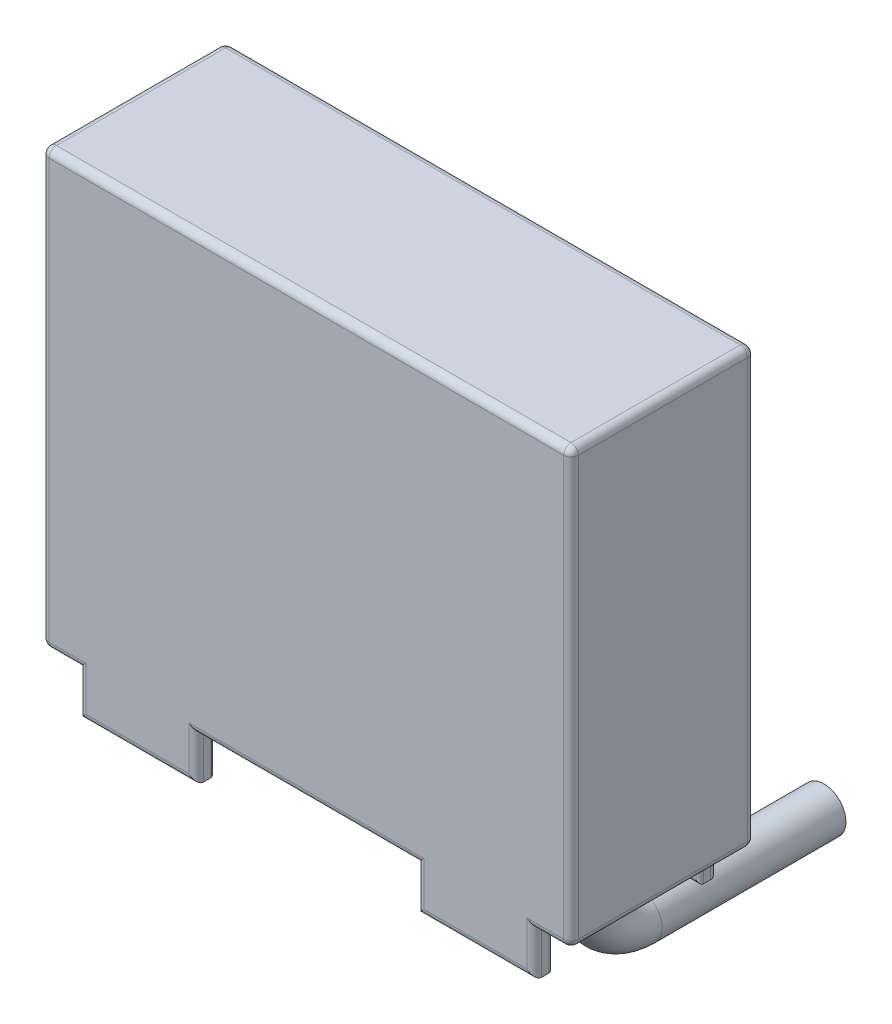
SolidWorks part; units mm, degrees
ref_plane "Front Plane" through (0, 0, 0) normal (0, 0, 1) x (1, 0, 0)
ref_plane "Top Plane" through (0, 0, 0) normal (0, 1, 0) x (1, 0, 0)
ref_plane "Right Plane" through (0, 0, 0) normal (1, 0, 0) x (0, 0, -1)
sketch "Sketch1" plane through (0, 0, 0) normal (0, 0, 1) x (1, 0, 0)
  line L1 (-3.6, 7) -> (3.6, 7)
  line L2 (-3.6, 7) -> (-3.6, 0.5)
  line L3 (-3.6, 0.5) -> (3.6, 0.5)
  line L4 (3.6, 7) -> (3.6, 0.5)
  line L5 (-3.6, 7) -> (3.6, 0.5) construction
  line L6 (-3.6, 0.5) -> (3.6, 7) construction
  point P0 (0, 3.75)
  dimension "D1" = 0.5
  dimension "D2" = 7.2
  dimension "D3" = 6.5
extrude "Boss-Extrude1" add sketch "Sketch1" along normal blind 2.5
sketch "Sketch5" plane through (0, 0.5, 0) normal (0, -1, 0) x (-1, 0, 0)
  line L0 (3.6, -2.5) -> (3.6, 0) construction
  line L1 (3.35, -2.25) -> (-3.35, -2.25)
  line L2 (3.35, -2.25) -> (3.35, -0.25)
  line L3 (3.35, -0.25) -> (-3.35, -0.25)
  line L4 (-3.35, -2.25) -> (-3.35, -0.25)
  line L5 (3.35, -2.25) -> (-3.35, -0.25) construction
  line L6 (3.35, -0.25) -> (-3.35, -2.25) construction
  line L7 (3.6, -2.5) -> (-3.6, -2.5) construction
  point P0 (0, -1.25)
  point P5 (3.35, -1.25)
  point P8 (3.6, -1.25)
  point P9 (0, -0.25)
  dimension "D1" = 0.25
  dimension "D2" = 0.25
extrude "Cut-Extrude1" cut sketch "Sketch5" against normal blind 0.7
sketch "Sketch6" plane through (0, 0, 2.5) normal (0, 0, 1) x (1, 0, 0)
  line L0 (-3.6, 0.5) -> (3.6, 0.5) construction
  line L1 (-1.5, 0.5) -> (1.5, 0.5)
  line L2 (-1.5, 0.5) -> (-1.5, 1.1)
  line L3 (-1.5, 1.1) -> (1.5, 1.1)
  line L4 (1.5, 0.5) -> (1.5, 1.1)
  line L6 (-3.6, 0.5) -> (-3.1, 0.5)
  line L7 (-3.6, 0.5) -> (-3.6, 1.1)
  line L8 (-3.6, 1.1) -> (-3.1, 1.1)
  line L9 (-3.1, 0.5) -> (-3.1, 1.1)
  line L10 (3.6, 0.5) -> (3.1, 0.5)
  line L11 (3.6, 0.5) -> (3.6, 1.1)
  line L12 (3.6, 1.1) -> (3.1, 1.1)
  line L13 (3.1, 0.5) -> (3.1, 1.1)
  point P16 (0, 0.5)
  dimension "D1" = 0.5
  dimension "D2" = 3
  dimension "D3" = 0.6
extrude "Cut-Extrude2" cut sketch "Sketch6" against normal blind 3
sketch "Sketch4" plane through (0, 1.2, 0) normal (0, -1, 0) x (1, 0, 0)
  line L0 (-2.54, 1.25) -> (2.54, 1.25) construction
  circle A0 centre (-2.54, 1.25) radius 0.3
  circle A1 centre (2.54, 1.25) radius 0.3
  point P2 (0, 1.25)
  dimension "D1" = 0.6
ref_plane "Plane1" through (-2.54, 0, 0) normal (1, 0, 0) x (0, 0, -1)
sketch "Sketch7" plane through (-2.54, 0, 0) normal (1, 0, 0) x (0, 0, -1)
  line L0 (-1.25, 1.2) -> (-1.25, 0.75)
  line L1 (-1.55, 1.2) -> (-0.95, 1.2) construction
  line L2 (-0.5, 0) -> (2, 0)
  arc A0 (-1.25, 0.75) -> (-0.5, 0) centre (-0.5, 0.75) ccw
  dimension "D2" = 0.75
  dimension "D1" = 2
sweep "Pin" add profiles "Sketch4" path "Sketch7"
fillet "Fillet1" radius 0.1 28 edges at (3.6, 7, 1.25) (3.6, 1.1, 1.25) (-3.6, 7, 1.25) (-3.6, 1.1, 1.25) (3.6, 4.05, 0) (0, 7, 0) (-3.6, 4.05, 0) (-3.35, 1.1, 0) (-3.1, 0.8, 0) (-2.3, 0.5, 0) (-1.5, 0.8, 0) (0, 1.1, 0) (1.5, 0.8, 0) (2.3, 0.5, 0) (3.1, 0.8, 0) (3.35, 1.1, 0) (2.3, 0.5, 2.5) (1.5, 0.8, 2.5) (0, 1.1, 2.5) (-1.5, 0.8, 2.5) (-2.3, 0.5, 2.5) (-3.1, 0.8, 2.5) (-3.35, 1.1, 2.5) (-3.6, 4.05, 2.5) (0, 7, 2.5) (3.6, 4.05, 2.5) (3.35, 1.1, 2.5) (3.1, 0.8, 2.5)
fillet "Fillet2" radius 0.05 30 edges at (-3.35, 1.1, 1.25) (3.35, 1.1, 1.25) (3.35, 1.15, 2.25) (0, 1.2, 2.25) (-3.35, 1.15, 2.25) (-3.225, 1.1, 2.25) (-3.1, 0.8, 2.25) (-2.3, 0.5, 2.25) (-1.5, 0.8, 2.25) (0, 1.1, 2.25) (1.5, 0.8, 2.25) (2.3, 0.5, 2.25) (3.1, 0.8, 2.25) (3.225, 1.1, 2.25) (1.5, 0.8, 0.25) (0, 1.1, 0.25) (-1.5, 0.8, 0.25) (-2.3, 0.5, 0.25) (-3.1, 0.8, 0.25) (-3.225, 1.1, 0.25) (-3.35, 1.15, 0.25) (0, 1.2, 0.25) (3.35, 1.15, 0.25) (3.225, 1.1, 0.25) (3.1, 0.8, 0.25) (2.3, 0.5, 0.25) (-3.35, 1.2, 1.25) (3.35, 1.2, 1.25) (-2.54, 1.2, 0.95) (2.54, 1.2, 0.95)
